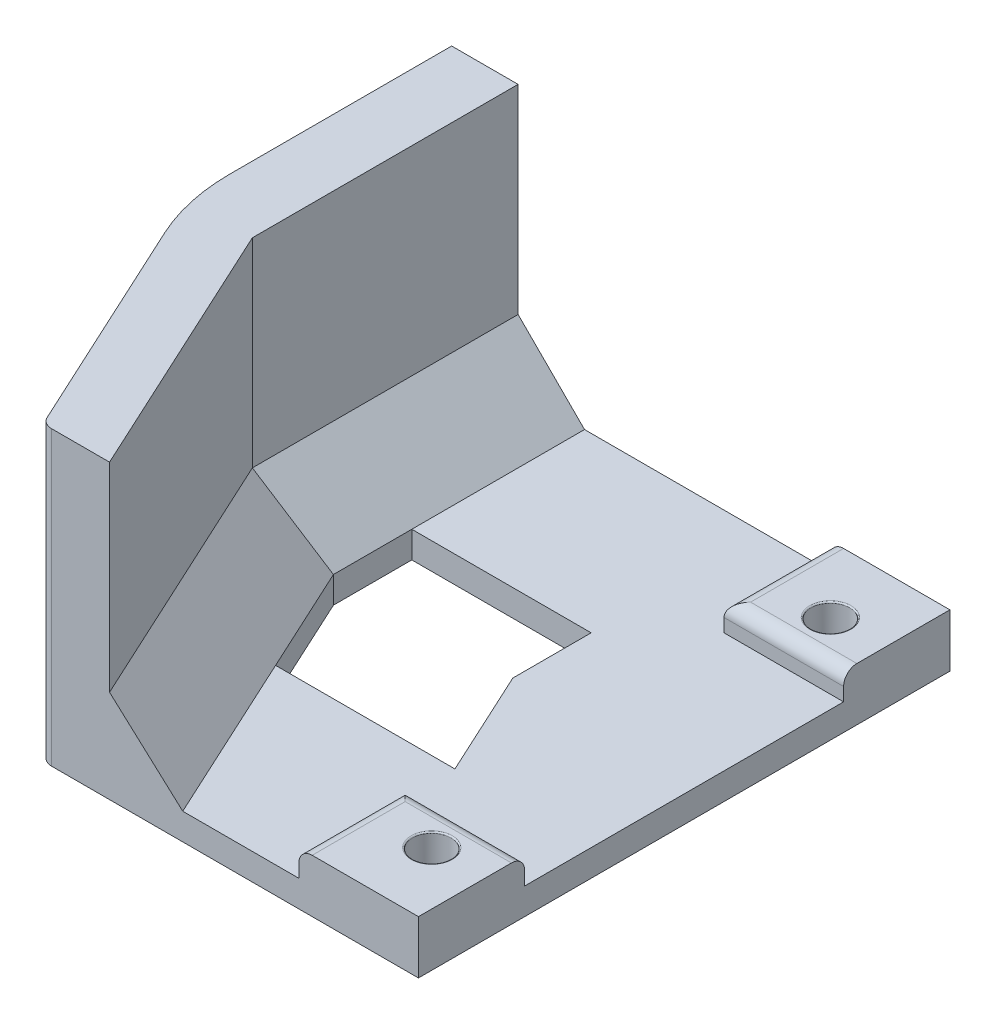
SolidWorks part; units mm, degrees
ref_plane "前视基准面" through (0, 0, 0) normal (0, 0, 1) x (1, 0, 0)
ref_plane "上视基准面" through (0, 0, 0) normal (0, 1, 0) x (1, 0, 0)
ref_plane "右视基准面" through (0, 0, 0) normal (1, 0, 0) x (0, 0, -1)
other "Configuration Table"
sketch "草图1" plane through (0, 0, 0) normal (0, 1, 0) x (1, 0, 0)
  line L1 (0, 0) -> (-57, 0)
  line L2 (0, 0) -> (0, 80)
  line L3 (0, 80) -> (-57, 80)
  line L4 (-57, 0) -> (-57, 80)
  dimension "D1" = 80
  dimension "D2" = 57
extrude "凸台-拉伸1" add sketch "草图1" along normal blind 4
sketch "草图2" plane through (0, 4, 0) normal (0, 1, 0) x (1, 0, 0)
  line L0 (-47, 40) -> (-28.5, 0)
  line L1 (-57, 80) -> (-47, 80)
  line L2 (-57, 80) -> (-57, 40)
  line L4 (-47, 80) -> (-47, 40)
  line L5 (-57, 0) -> (0, 0) construction
  line L6 (-28.5, 0) -> (-38.5, 0)
  line L7 (-38.5, 0) -> (-57, 40)
  dimension "D1" = 10
  dimension "D2" = 40
  dimension "D3" = 10
extrude "凸台-拉伸2" add sketch "草图2" along normal blind 40
sketch "草图3" plane through (0, 4, 0) normal (0, 1, 0) x (1, 0, 0)
  line L3 (-38.5, 0) -> (-57, 40)
  line L4 (-57, 40) -> (-57, 0)
  line L5 (-57, 0) -> (-38.5, 0)
  line L6 (-38.5, 0) -> (-57, 40)
  line L7 (-57, 40) -> (-57, 0)
  line L8 (-57, 0) -> (-38.5, 0)
  dimension "D1" = 0
extrude "切除-拉伸1" cut sketch "草图3" against normal blind 16
sketch "草图4" plane through (0, 0, 0) normal (1, 0, 0) x (0, 0, -1)
  line L4 (0, 0) -> (80, 0)
  line L5 (80, 0) -> (80, 4)
  line L6 (80, 4) -> (0, 4)
  line L7 (0, 4) -> (0, 0)
  line L8 (0, 0) -> (80, 0)
  line L9 (80, 0) -> (80, 4)
  line L10 (80, 4) -> (0, 4)
  line L11 (0, 4) -> (0, 0)
  dimension "D1" = 0
extrude "凸台-拉伸3" add sketch "草图4" along normal blind 20
sketch "草图7" plane through (0, 4, 0) normal (0, 1, 0) x (1, 0, 0)
  line L0 (-28.5, 0) -> (20, 0) construction
  line L1 (20, 80) -> (0, 80)
  line L2 (20, 80) -> (20, 0)
  line L3 (20, 0) -> (0, 0)
  line L4 (0, 80) -> (0, 0)
  dimension "D1" = 20
extrude "凸台-拉伸4" add sketch "草图7" along normal blind 4
sketch "草图5" plane through (0, 4, 0) normal (0, 1, 0) x (1, 0, 0)
  line L0 (20, 40) -> (-21.588, 40) construction
  line L1 (20, 80) -> (20, 0) construction
  line L2 (20, 80) -> (10, 80) construction
  line L3 (0, 80) -> (-47, 80) construction
  line L4 (10, 80) -> (10, 70) construction
  circle A0 centre (10, 70) radius 1.45
  circle A1 centre (10, 10) radius 1.45
  dimension "D3" = 2.9
  dimension "D1" = 10
  dimension "D2" = 10
extrude "切除-拉伸2" cut sketch "草图5" against normal blind 4 and the other way blind 4
sketch "草图8" plane through (0, 8, 0) normal (0, 1, 0) x (1, 0, 0)
  circle A0 centre (10, 70) radius 2.9
  circle A1 centre (10, 10) radius 2.9
  dimension "D1" = 5.8
  dimension "D2" = 5.8
extrude "切除-拉伸3" cut sketch "草图8" against normal blind 6
sketch "草图9" plane through (20, 0, 0) normal (1, 0, 0) x (0, 0, -1)
  line L4 (0, 8) -> (0, 0)
  line L5 (0, 0) -> (80, 0)
  line L6 (80, 0) -> (80, 8)
  line L7 (80, 8) -> (0, 8)
  line L8 (0, 8) -> (0, 0)
  line L9 (0, 0) -> (80, 0)
  line L10 (80, 0) -> (80, 8)
  line L11 (80, 8) -> (0, 8)
  dimension "D1" = 0
extrude "切除-拉伸4" cut sketch "草图9" against normal blind 2
sketch "草图10" plane through (0, 8, 0) normal (0, 1, 0) x (1, 0, 0)
  line L0 (0, 80) -> (0, 0) construction
  line L1 (0, 64) -> (18, 64)
  line L2 (0, 64) -> (0, 16)
  line L3 (0, 16) -> (18, 16)
  line L4 (18, 64) -> (18, 16)
  line L5 (18, 80) -> (18, 0) construction
  line L6 (18, 80) -> (0, 80) construction
  line L7 (0, 0) -> (18, 0) construction
  dimension "D1" = 16
  dimension "D2" = 16
extrude "切除-拉伸5" cut sketch "草图10" against normal up to surface (4 mm away) up to face at (-24.5, 4, -40)
sketch "草图11" plane through (0, 4, 0) normal (0, 1, 0) x (1, 0, 0)
  line L0 (-37, 42.2005) -> (-29.5073, 26)
  line L2 (-37, 42.2005) -> (-37, 54)
  line L3 (-37, 54) -> (-10, 54)
  line L4 (-10, 42.2005) -> (-10, 54)
  line L5 (-29.5073, 26) -> (-2.5073, 26)
  line L6 (-2.5073, 26) -> (-10, 42.2005)
  line L7 (-28.5, 0) -> (-47, 40) construction
  line L8 (0, 80) -> (0, 64) construction
  line L10 (-47, 40) -> (-47, 80) construction
  line L11 (18, 16) -> (0, 16) construction
  line L13 (0, 64) -> (18, 64) construction
  point P18 (0, 0)
  dimension "D1" = 10
  dimension "D2" = 10
  dimension "D3" = 10
  dimension "D4" = 10
  dimension "D5" = 10
extrude "切除-拉伸6" cut sketch "草图11" against normal up to surface (4 mm away) up to face at (10, 0, -11.45)
chamfer "倒角1" distance 10 angle 45 2 edges at (-37.75, 4, -20) (-47, 4, -60)
fillet "圆角1" radius 30 1 edges at (-57, 22, -40)
fillet "圆角2" radius 2 5 edges at (0, 8, -8) (9, 8, -16) (0, 8, -72) (9, 8, -64) (-38.5, 22, 0)
fillet "圆角3" radius 0.2 4 edges at (10, 2, -68.55) (10, 8, -67.1) (10, 2, -8.55) (10, 8, -7.1)
